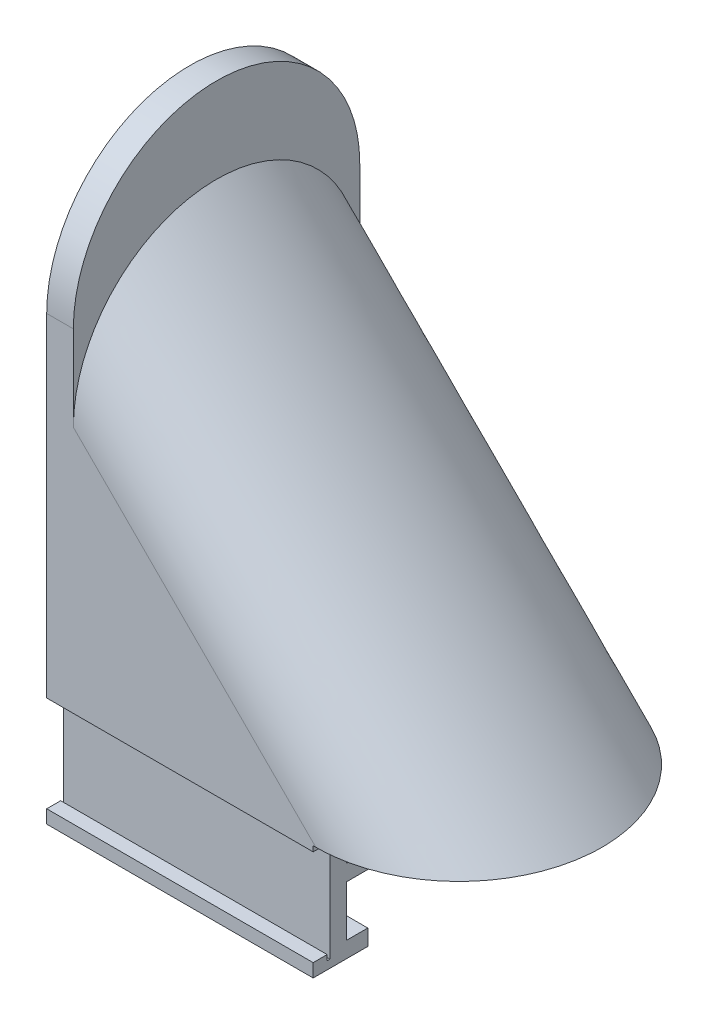
SolidWorks part; units mm, degrees
ref_plane "前视" through (0, 0, 0) normal (0, 0, 1) x (1, 0, 0)
ref_plane "上视" through (0, 0, 0) normal (0, 1, 0) x (1, 0, 0)
ref_plane "右视" through (0, 0, 0) normal (1, 0, 0) x (0, 0, -1)
sketch "Sketch1" plane through (0, 0, 0) normal (0, 1, 0) x (1, 0, 0)
  line L0 (0, 0) -> (9.3, 0)
  line L1 (9.3, 8.25) -> (0, 8.25)
  line L2 (0, 0) -> (0, -1.25)
  line L3 (0, -1.25) -> (9.3, -1.25)
  line L4 (9.3, 9.5) -> (0, 9.5)
  line L5 (0, 9.5) -> (0, 8.25)
  arc A0 (9.3, 0) -> (9.3, 8.25) centre (9.3, 4.125) ccw
  arc A1 (9.3, -1.25) -> (9.3, 9.5) centre (9.3, 4.125) ccw
  dimension "D2" = 4.125
  dimension "D4" = 5.375
  dimension "D1" = 9.3
  dimension "D3" = 1.25
sketch "Sketch2" plane through (0, 0, 0) normal (0, 0, 1) x (1, 0, 0)
  line L0 (0, 0) -> (-15, 15)
  dimension "D1" = 15
sweep "Sweep1" add profiles "Sketch1" path "Sketch2"
ref_axis "Axis1" through (0, 0, 1.25) along (0, 0, -1)
ref_plane "Plane1" through (0, 0, 0) normal (-1, 0, 0) x (0, 0, -1)
sketch "Sketch3" plane through (0, 0, 0) normal (-1, 0, 0) x (0, 0, -1)
  line L1 (14.2268, -27.5531) -> (-8.6374, -27.5531)
  line L2 (14.2268, -27.5531) -> (14.2268, 0.6106)
  line L3 (14.2268, 0.6106) -> (-8.6374, 0.6106)
  line L4 (-8.6374, -27.5531) -> (-8.6374, 0.6106)
extrude "Cut-Extrude1" cut sketch "Sketch3" along normal through all
sketch "Sketch5" plane through (0, 0, 0) normal (-1, 0, 0) x (0, 0, -1)
  line L0 (9.5, 0) -> (9.5, -12.5)
  line L1 (-1.25, 0) -> (-1.25, -12.5)
  line L2 (9.5, 0) -> (8.25, 0)
  line L3 (8.25, 0) -> (8.25, -9.3)
  line L4 (-1.25, 0) -> (0, 0)
  line L5 (0, 0) -> (0, -9.3)
  arc A0 (9.5, -12.5) -> (-1.25, -12.5) centre (4.125, -12.5) cw
  arc A1 (8.25, -9.3) -> (0, -9.3) centre (4.125, -9.3) cw
  dimension "D1" = 12.5
  dimension "D2" = 12.5
extrude "Boss-Extrude1" add sketch "Sketch5" along normal blind 1
sketch "Sketch6" plane through (0, 0, 0) normal (0, -1, 0) x (1, 0, 0)
  line L0 (-1, -8.875) -> (9.0015, -8.875)
  line L1 (-1, -9.5) -> (-1, -8.25) construction
  line L2 (9.0015, -8.875) -> (9.0015, -8.25)
  line L3 (-1, -8.25) -> (9.3, -8.25) construction
  line L4 (9.0015, -8.25) -> (-1, -8.25)
  line L5 (-1, -8.25) -> (-1, -8.875)
  line L6 (-1, 0) -> (-1, 0.625)
  line L7 (-1, 0) -> (-1, 1.25) construction
  line L8 (-1, 0.625) -> (9.0015, 0.625)
  line L9 (9.0015, 0.625) -> (9.0015, 0)
  line L10 (9.3, 0) -> (-1, 0) construction
  line L11 (9.0015, 0) -> (-1, 0)
extrude "Boss-Extrude2" add sketch "Sketch6" along normal blind 3.6
sketch "Sketch7" plane through (0, -3.6, 0) normal (0, -1, 0) x (1, 0, 0)
  line L0 (-1, 1.25) -> (-1, 0)
  line L1 (-1, 0) -> (9.0015, 0)
  line L2 (9.0015, 0) -> (9.0015, 1.25)
  line L3 (-1, 1.25) -> (9.3, 1.25) construction
  line L4 (9.0015, 1.25) -> (-1, 1.25)
  line L5 (-1, -8.25) -> (-1, -9.5)
  line L6 (-1, -9.5) -> (9.0015, -9.5)
  line L7 (9.3, -9.5) -> (-1, -9.5) construction
  line L8 (9.0015, -9.5) -> (9.0015, -8.25)
  line L9 (9.0015, -8.25) -> (-1, -8.25)
extrude "Boss-Extrude3" add sketch "Sketch7" along normal blind 0.5
ref_plane "Plane3" through (0, -1, 0) normal (0, -1, 0) x (-1, 0, 0)
sketch "Sketch8" plane through (0, -1, 0) normal (0, -1, 0) x (-1, 0, 0)
  line L0 (-9.0015, 8.25) -> (-9.0015, 0)
  line L1 (-9.0015, 0) -> (-3.5015, 0)
  line L2 (0, 0) -> (-9.3, 0) construction
  line L3 (-3.5015, 0) -> (1, 0)
  line L4 (1, 0) -> (1, 0.8)
  line L5 (1, 0.8) -> (-3.5015, 0.8)
  line L6 (-3.5015, 0.8) -> (-3.5015, 2.875)
  line L7 (-3.5015, 8.25) -> (1, 8.25)
  line L8 (-9.0015, 8.25) -> (1, 8.25) construction
  line L10 (-3.5015, 5.375) -> (1, 5.375)
  line L11 (1, 0) -> (1, 8.25) construction
  line L12 (1, 5.375) -> (1, 2.875)
  line L13 (1, 2.875) -> (-3.5015, 2.875)
  line L14 (-9.0015, 8.25) -> (-3.5015, 8.25)
  line L15 (1, 8.25) -> (1, 7.45)
  line L16 (1, 7.45) -> (-3.5015, 7.45)
  line L17 (-3.5015, 7.45) -> (-3.5015, 5.375)
  dimension "D1" = 5.5
  dimension "D2" = 2.875
  dimension "D3" = 2.875
  dimension "D4" = 0.8
  dimension "D5" = 0.8
extrude "Boss-Extrude4" add sketch "Sketch8" along normal blind 0.6
ref_plane "Plane4" through (0, 0.2, 0) normal (0, -1, 0) x (-1, 0, 0)
sketch "Sketch9" plane through (0, 0.2, 0) normal (0, -1, 0) x (-1, 0, 0)
  line L0 (1, -0.625) -> (-9.0015, -0.625)
  line L1 (1, -1.25) -> (1, 0) construction
  line L2 (-9.0015, -0.625) -> (-9.0015, -0.725)
  line L3 (-9.0015, 0) -> (-9.0015, -1.25) construction
  line L4 (-9.0015, -0.725) -> (1, -0.725)
  line L5 (1, -0.725) -> (1, -0.625)
  line L6 (1, 8.875) -> (-9.0015, 8.875)
  line L7 (1, 8.25) -> (1, 9.5) construction
  line L8 (-9.0015, 9.5) -> (-9.0015, 8.25) construction
  line L9 (-9.0015, 8.875) -> (-9.0015, 8.975)
  line L10 (-9.0015, 8.975) -> (1, 8.975)
  line L11 (1, 8.975) -> (1, 8.875)
  dimension "D1" = 0.1
  dimension "D2" = 0.1
extrude "Cut-Extrude2" cut sketch "Sketch9" along normal blind 4
sketch "Sketch10" plane through (0, 0, 0) normal (0, -1, 0) x (1, 0, 0)
  line L0 (9.0015, 0.725) -> (9.0015, -8.875)
  line L1 (9.0015, -8.875) -> (9.0015, -10.301)
  line L2 (9.0015, -10.301) -> (15.9666, -10.301)
  line L3 (15.9666, -10.301) -> (15.9666, 1.7435)
  line L4 (15.9666, 1.7435) -> (9.0015, 1.7435)
  line L5 (9.0015, 1.7435) -> (9.0015, 0.725)
extrude "Cut-Extrude3" cut sketch "Sketch10" against normal blind 0.2
sketch "Sketch12" plane through (0, -4.1, 0) normal (0, -1, 0) x (1, 0, 0)
  line L0 (-1, -8.25) -> (-1, -7.45)
  line L1 (9.0015, -7.45) -> (-1, -7.45)
  line L2 (9.0015, -8.25) -> (9.0015, -7.45)
  line L3 (9.0015, -8.25) -> (-1, -8.25)
  line L4 (9.0015, 0) -> (9.0015, -0.8)
  line L5 (9.0015, -0.8) -> (-1, -0.8)
  line L6 (-1, -0.8) -> (-1, 0)
  line L7 (-1, 0) -> (9.0015, 0)
  dimension "D1" = 0.8
  dimension "D2" = 0.8
  dimension "D3" = 0.8
extrude "Boss-Extrude5" add sketch "Sketch12" against normal blind 0.6
